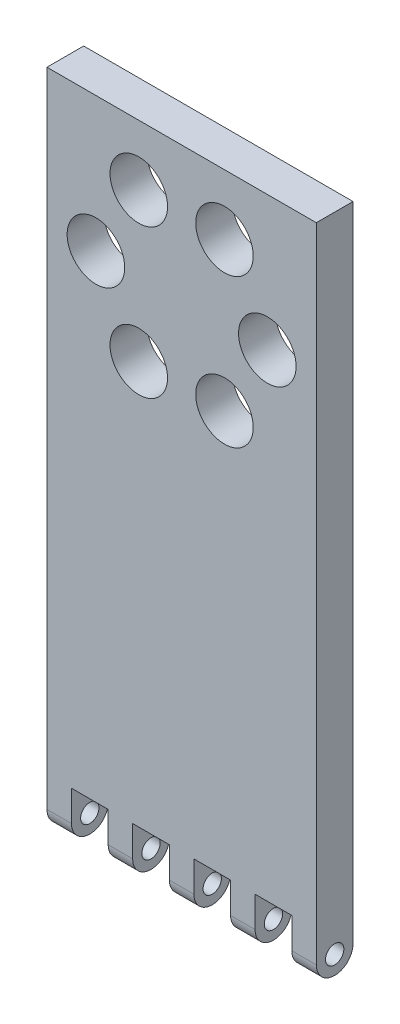
SolidWorks part; units mm, degrees
ref_plane "Front Plane" through (0, 0, 0) normal (0, 0, 1) x (1, 0, 0)
ref_plane "Top Plane" through (0, 0, 0) normal (0, 1, 0) x (1, 0, 0)
ref_plane "Right Plane" through (0, 0, 0) normal (1, 0, 0) x (0, 0, -1)
sketch "Sketch1" plane through (0, 0, 0) normal (0, 0, 1) x (1, 0, 0)
  line L1 (-22, 50) -> (22, 50)
  line L2 (-22, 50) -> (-22, -50)
  line L3 (-22, -50) -> (22, -50)
  line L4 (22, 50) -> (22, -50)
  line L5 (-22, 50) -> (22, -50) construction
  line L6 (-22, -50) -> (22, 50) construction
  point P0 (0, 0)
extrude "Boss-Extrude1" add sketch "Sketch1" along normal blind 6
sketch "Sketch3" plane through (0, 0, 6) normal (0, 0, 1) x (1, 0, 0)
  line L0 (-22, 50) -> (-22, -50) construction
  line L1 (22, 50) -> (-22, 50) construction
  line L2 (22, 50) -> (-22, 50) construction
  line L3 (22, -50) -> (22, 50) construction
  circle A0 centre (-7.0026, 40.1234) radius 4.7
  circle A1 centre (6.9974, 40.1234) radius 4.7
  circle A2 centre (13.9974, 27.999) radius 4.7
  circle A3 centre (6.9974, 15.8746) radius 4.7
  circle A4 centre (-7.0026, 15.8746) radius 4.7
  circle A5 centre (-14.0026, 27.999) radius 4.7
  point P0 (0, 28)
  dimension "D1" = 22
  dimension "D2" = 22
  dimension "D3" = 9.8766
  dimension "D4" = 8.0026
extrude "Cut-Extrude4" cut sketch "Sketch3" against normal blind 10
sketch "Sketch4" plane through (0, -50, 0) normal (0, -1, 0) x (1, 0, 0)
  line L0 (-22, 0) -> (22, 0) construction
  line L1 (-22, 6) -> (-18, 6)
  line L2 (-22, 6) -> (-22, 0)
  line L3 (-22, 0) -> (-18, 0)
  line L4 (-18, 6) -> (-18, 0)
  line L5 (-20, 0) -> (-20, 6) construction
  line L6 (-22, 3) -> (-18, 3) construction
  point P380 (-20, 3)
extrude "Boss-Extrude2" add sketch "Sketch4" along normal blind 8
fillet "Fillet1" radius 3 2 edges at (-20, -58, 6) (-20, -58, 0)
pattern_linear "LPattern1" count 5 spacing 10 along (1, 0, 0) of "Fillet1", "Boss-Extrude2"
sketch "Sketch5" plane through (-22, 0, 0) normal (-1, 0, 0) x (0, 0, 1)
  circle A0 centre (3, -55) radius 1.5
  arc A1 (0, -55) -> (3, -58) centre (3, -55) ccw construction
  dimension "D1" = 0
extrude "Cut-Extrude5" cut sketch "Sketch5" against normal through all
